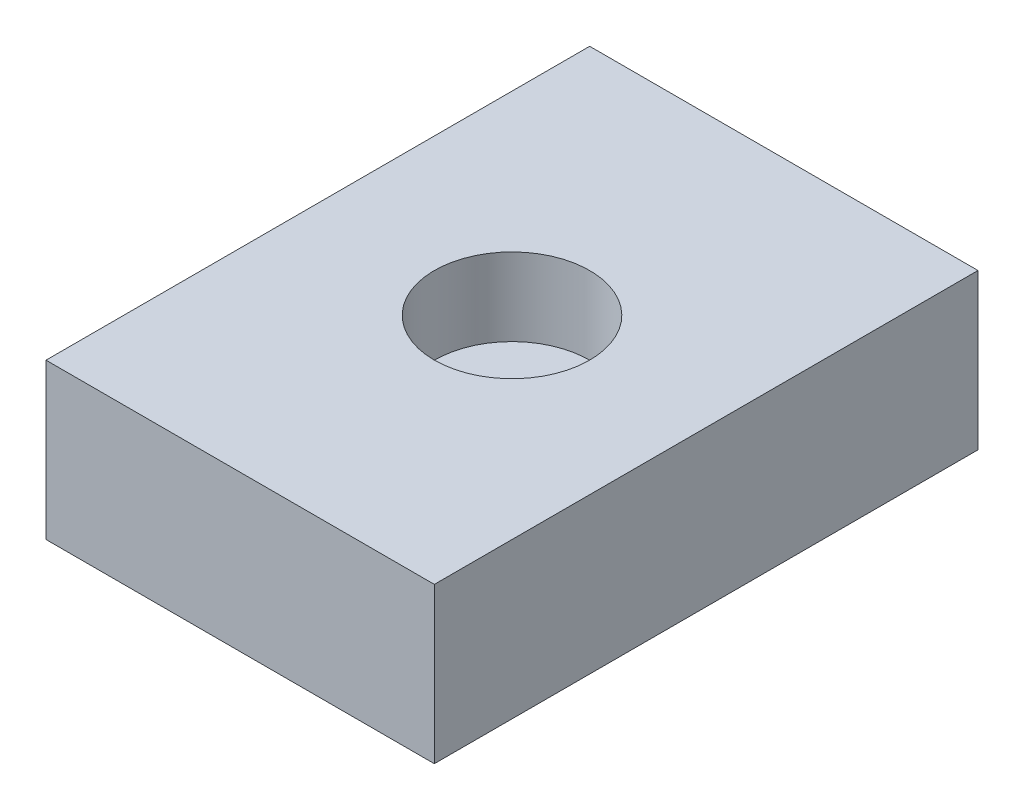
SolidWorks part; units mm, degrees
ref_plane "Front Plane" through (0, 0, 0) normal (0, 0, 1) x (1, 0, 0)
ref_plane "Top Plane" through (0, 0, 0) normal (0, 1, 0) x (1, 0, 0)
ref_plane "Right Plane" through (0, 0, 0) normal (1, 0, 0) x (0, 0, -1)
sketch "Sketch1" plane through (0, 0, 0) normal (0, 1, 0) x (1, 0, 0)
  line L1 (-31.75, 44.45) -> (31.75, 44.45)
  line L2 (-31.75, 44.45) -> (-31.75, -44.45)
  line L3 (-31.75, -44.45) -> (31.75, -44.45)
  line L4 (31.75, 44.45) -> (31.75, -44.45)
  point P4 (0, 44.45)
  point P7 (-31.75, 0)
  dimension "D1" = 88.9
  dimension "D2" = 63.5
extrude "Boss-Extrude1" add sketch "Sketch1" along normal blind 25.4 contours L2 L3 L4 L1
sketch "Sketch3" plane through (0, 25.4, 0) normal (0, 1, 0) x (1, 0, 0)
  circle A0 centre (0, 0) radius 12.7
  dimension "D1" = 25.4
extrude "Cut-Extrude1" cut sketch "Sketch3" against normal blind 12.7
ref_axis "Axis1" through (0, 12.7, 0) along (0, 1, 0)
